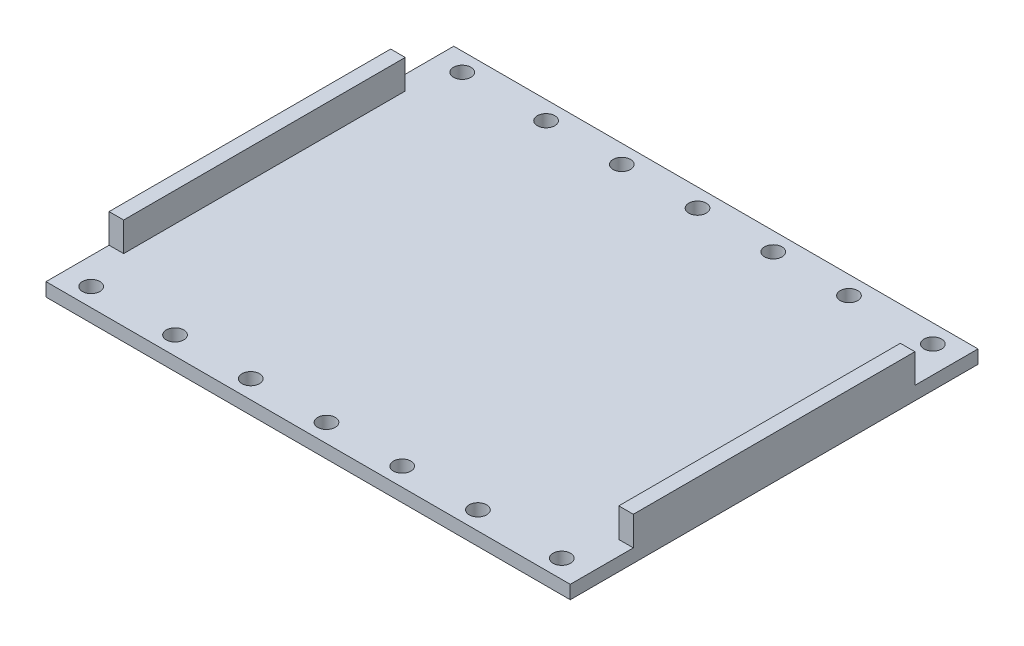
SolidWorks part; units mm, degrees
ref_plane "前视基准面" through (0, 0, 0) normal (0, 0, 1) x (1, 0, 0)
ref_plane "上视基准面" through (0, 0, 0) normal (0, 1, 0) x (1, 0, 0)
ref_plane "右视基准面" through (0, 0, 0) normal (1, 0, 0) x (0, 0, -1)
sketch "草图1" plane through (0, 0, 0) normal (0, 1, 0) x (1, 0, 0)
  line L0 (-45, 0) -> (45, 0) construction
  line L1 (-45, 35) -> (45, 35)
  line L2 (-45, 35) -> (-45, -35)
  line L3 (-45, -35) -> (45, -35)
  line L4 (45, 35) -> (45, -35)
  line L5 (-45, 35) -> (45, -35) construction
  line L6 (-45, -35) -> (45, 35) construction
  line L7 (0, -35) -> (0, 35) construction
  circle A0 centre (40.4, -31.85) radius 1.5
  circle A1 centre (-40.4, -31.85) radius 1.5
  circle A2 centre (40.4, 31.85) radius 1.5
  circle A3 centre (-40.4, 31.85) radius 1.5
  point P0 (0, 0)
  point P11 (0, 0)
  point P16 (0, 0)
  dimension "D3" = 1.65
  dimension "D4" = 3
  dimension "D5" = 3.1
  dimension "D1" = 70
  dimension "D2" = 90
extrude "凸台-拉伸1" add sketch "草图1" along normal blind 2.3
sketch "草图2" plane through (0, 2.3, 0) normal (0, 1, 0) x (1, 0, 0)
  line L0 (45, 0) -> (-45, 0) construction
  line L1 (45, -35) -> (45, 35) construction
  line L2 (-45, 35) -> (-45, -35) construction
  line L4 (42.5, -24.17) -> (45, -24.17)
  line L5 (42.5, -24.17) -> (42.5, 24.17)
  line L6 (42.5, 24.17) -> (45, 24.17)
  line L7 (45, -24.17) -> (45, 24.17)
  line L8 (42.5, -24.17) -> (45, 24.17) construction
  line L9 (42.5, 24.17) -> (45, -24.17) construction
  point P6 (43.75, 0)
  dimension "D1" = 2.5
  dimension "D2" = 48.34
extrude "凸台-拉伸2" add sketch "草图2" along normal blind 5
ref_plane "基准面1" through (0, 0, 0) normal (1, 0, 0) x (0, 0, -1)
mirror "镜向1" about plane through (0, 0, 0) normal (1, 0, 0) of "凸台-拉伸2"
sketch "草图4" plane through (0, 0, 0) normal (0, -1, 0) x (1, 0, 0)
  line L0 (-40.4, 31.85) -> (40.4, 31.85) construction
  line L4 (0, -4.015) -> (0, 4.015) construction
  circle A9 centre (0, 31.85) radius 1.5
  point P6 (0, 31.35)
  point P7 (0, 31.85)
  point P11 (0, 32.85)
  dimension "D1" = 3
extrude "切除-拉伸1" cut sketch "草图4" against normal blind 10
ref_plane "基准面2" through (0, 0, 0) normal (0, 0, 1) x (1, 0, 0)
pattern_linear "阵列(线性)1" count 3 spacing 13 along (-1, 0, 0) count 3 spacing 13 along (1, 0, 0) of "切除-拉伸1"
mirror "镜向2" about plane through (0, 0, 0) normal (0, 0, 1) of "阵列(线性)1", "切除-拉伸1"
